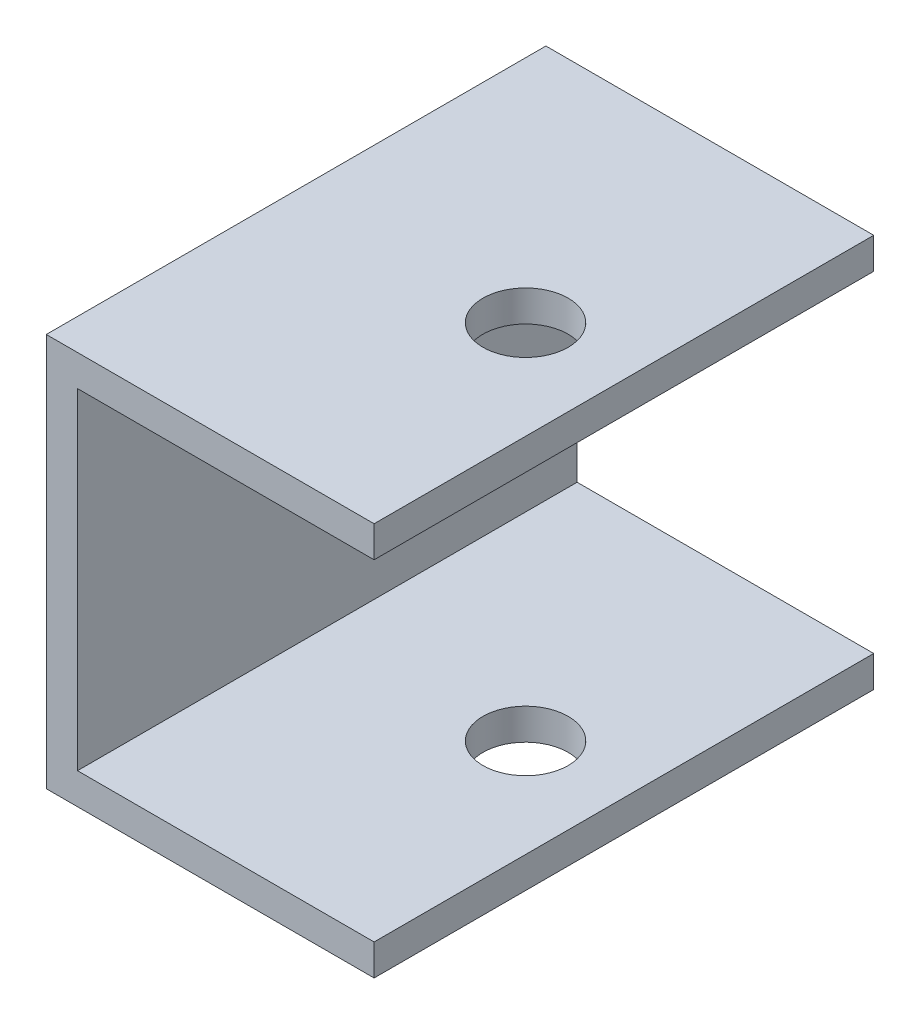
SolidWorks part; units mm, degrees
material "AISI 1020 Acero laminado en frío"
ref_plane "Alzado" through (0, 0, 0) normal (0, 0, 1) x (1, 0, 0)
ref_plane "Planta" through (0, 0, 0) normal (0, 1, 0) x (1, 0, 0)
ref_plane "Vista lateral" through (0, 0, 0) normal (1, 0, 0) x (0, 0, -1)
sketch "Croquis6" plane through (0, 0, 0) normal (0, 0, 1) x (1, 0, 0)
  line L0 (45.2375, 25.2375) -> (0, 25.2375)
  line L1 (0, 25.2375) -> (0, -25.2375)
  line L2 (0, -25.2375) -> (45.2375, -25.2375)
  line L3 (45.2375, -25.2375) -> (45.2375, -30)
  line L4 (45.2375, -30) -> (-4.7625, -30)
  line L5 (-4.7625, -30) -> (-4.7625, 30)
  line L6 (-4.7625, 30) -> (45.2375, 30)
  line L7 (45.2375, 30) -> (45.2375, 25.2375)
  point P3 (0, 0)
  dimension "D1" = 4.7625
  dimension "D2" = 4.7625
  dimension "D3" = 4.7625
  dimension "D4" = 60
  dimension "D5" = 50
extrude "Saliente-Extruir3" add sketch "Croquis6" along normal mid plane 76.2
sketch "Croquis7" plane through (-4.7625, 0, 0) normal (-1, 0, 0) x (0, 0, 1)
  circle A0 centre (0, 0) radius 5.5562
  dimension "D1" = 11.1125
extrude "Cortar-Extruir1" cut sketch "Croquis7" against normal blind 5 contours A0
sketch "Croquis8" plane through (0, -30, 0) normal (0, -1, 0) x (1, 0, 0)
  line L0 (0, 0) -> (31.2543, 0) construction
  line L3 (45.2375, 38.1) -> (45.2375, -38.1) construction
  circle A0 centre (30.2375, 0) radius 6.5
  dimension "D1" = 13
  dimension "D2" = 15
extrude "Cortar-Extruir2" cut sketch "Croquis8" against normal blind 70 contours A0
